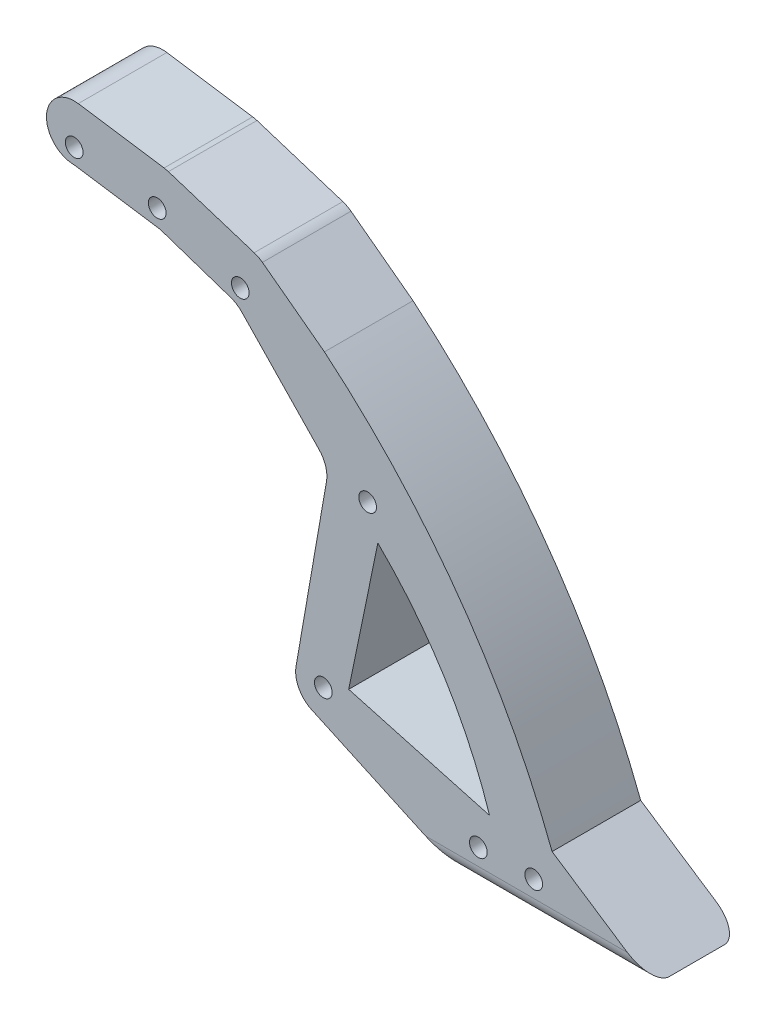
SolidWorks part; units mm, degrees
note: The reader was unsure of these and kept them because the rebuilt part matched: shared geometry of "Sketch2<4>".
ref_plane "Front Plane" through (0, 0, 0) normal (0, 0, 1) x (1, 0, 0)
ref_plane "Top Plane" through (0, 0, 0) normal (0, 1, 0) x (1, 0, 0)
ref_plane "Right Plane" through (0, 0, 0) normal (1, 0, 0) x (0, 0, -1)
sketch "Sketch1" plane through (0, 0, 0) normal (0, 0, 1) x (1, 0, 0)
  line L0 (41.32, -5) -> (59.46, -17)
  line L1 (25, -17) -> (59.46, -17)
  line L5 (-12.4827, 61.7642) -> (-27.9827, 66.7007)
  line L6 (-28.7619, 66.8817) -> (-44.2619, 69.1952)
  line L7 (25, -17) -> (-2.089, -4.5427)
  line L8 (-45, 59.25) -> (-29.5, 56.9365)
  line L9 (0.2, 52.6) -> (-11, 61) construction
  line L10 (-29.5, 56.9365) -> (-15.5935, 52.2607)
  line L11 (-15.5935, 52.2607) -> (1, 35)
  line L12 (-28.7619, 66.8817) -> (-27.9827, 66.7007)
  line L13 (9.8511, 27.5193) -> (4.5811, 2.0033)
  line L14 (4.5811, 2.0033) -> (30.0199, -5)
  line L15 (-4.9263, 0.855) -> (1, 35) construction
  line L17 (-11, 61) -> (0.2, 52.6)
  line L18 (-4.9263, 0.855) -> (1, 35)
  circle A0 centre (0, 0) radius 1.6
  circle A1 centre (-15, 55) radius 1.6
  circle A2 centre (-30, 60) radius 1.6
  circle A4 centre (-45, 62) radius 1.6
  circle A5 centre (28, -11) radius 1.6
  circle A6 centre (38, -11) radius 1.6
  circle A7 centre (0, 0) radius 5
  circle A12 centre (-29.5, 61.9365) radius 5 construction
  circle A13 centre (-14, 57) radius 5 construction
  arc A14 (-44.2619, 69.1952) -> (-45, 59.25) centre (-45, 64.25) ccw
  arc A15 (-12.4827, 61.7642) -> (-11, 61) centre (-14, 57) cw
  arc A16 (0.2, 52.6) -> (41.32, -5) centre (-89.4843, -54.9022) cw
  arc A17 (9.8511, 27.5193) -> (30.0199, -5) centre (-46.0773, -29.6821) cw
  circle A18 centre (8, 33) radius 1.6
  point P15 (42.23, -11)
  dimension "D1" = 3.2
  dimension "D3" = 3.2
  dimension "D11" = 3.2
  dimension "D12" = 140
  dimension "D13" = 28
  dimension "D16" = 3.2
  dimension "D17" = 3.2
  dimension "D18" = 3.2
  dimension "D24" = 11.2
  dimension "D25" = 10
  dimension "D26" = 1
  dimension "D27" = 2
  dimension "D20" = 10
  dimension "D4" = 10
  dimension "D5" = 10
  dimension "D37" = 10
  dimension "D38" = 3.2
  dimension "D2" = 55
  dimension "D6" = 62
  dimension "D7" = 45
  dimension "D8" = 30
  dimension "D9" = 60
  dimension "D10" = 15
  dimension "D14" = 38
  dimension "D15" = 11
  dimension "D19" = 11
  dimension "D21" = 3
  dimension "D22" = 21.46
  dimension "D23" = 3.32
  dimension "D28" = 6
  dimension "D29" = 6
  dimension "D30" = 8.4
  dimension "D31" = 0.5
  dimension "D32" = 2
  dimension "D33" = 0
  dimension "D34" = 2.25
  dimension "D35" = 35
  dimension "D36" = 1
  dimension "D39" = 33
  dimension "D40" = 8
extrude "Boss-Extrude1" add sketch "Sketch1" along normal blind 16
fillet "Fillet1" radius 3 2 edges at (42.23, -17, 0) (42.23, -17, 16)
fillet "Fillet2" radius 5 3 edges at (1, 35, 8) (-29.5, 56.9365, 8) (-15.5935, 52.2607, 8)
sketch "Sketch2" plane through (0, 0, 16) normal (0, 0, 1) x (1, 0, 0)
  line L0 (-17.9796, 59.0152) -> (-23.4996, 54.919)
  line L5 (-10, 55) -> (-10, 46.4423)
  line L6 (-29.0814, 56.7957) -> (-16.7552, 52.6513) construction
  line L7 (-23.4996, 54.919) -> (-10, 46.4423)
  line L8 (-33.6358, 63.4323) -> (-38.5, 58.2798)
  line L9 (-25.1633, 61.2675) -> (-23.4996, 54.919)
  line L10 (-38.5, 58.2798) -> (-23.4996, 54.919)
  line L11 (-45, 59.25) -> (-29.9368, 57.0017) construction
  line L12 (-13.2054, 53.9095) -> (-14.7441, 51.3772)
  line L13 (-16.7998, 56.0821) -> (-18.5081, 53.2407)
  line L14 (-32.0814, 60.2786) -> (-32.4695, 57.3797)
  line L15 (-27.9194, 59.7155) -> (-28.3521, 56.5505)
  line L17 (-40.2538, 63.5727) -> (-38.5, 58.2798)
  line L19 (-42.9322, 61.6338) -> (-43.3967, 59.0107)
  line L20 (-47.0684, 62.363) -> (-47.4974, 59.9184)
  line L21 (-14.7441, 51.3772) -> (-0.7548, 36.8254) construction
  circle A0 centre (-30, 60) radius 5
  circle A1 centre (-15, 55) radius 5
  circle A2 centre (-30, 60) radius 1.6 construction
  circle A3 centre (-15, 55) radius 2.1
  circle A4 centre (-30, 60) radius 2.1
  circle A5 centre (-45, 62) radius 5
  circle A6 centre (-45, 62) radius 2.1
  circle A7 centre (-45, 62) radius 1.6 construction
  arc A8 (-44.2619, 69.1952) -> (-45, 59.25) centre (-45, 64.25) ccw construction
  circle M25 centre (-45, 62) radius 1.6
  circle M26 centre (-30, 60) radius 1.6
  circle M27 centre (-15, 55) radius 1.6
  arc M32 (-44.2619, 69.1952) -> (-45, 59.25) centre (-45, 64.25) ccw
  line M33 (-45, 59.25) -> (-29.9368, 57.0017)
  arc M34 (-29.9368, 57.0017) -> (-29.0814, 56.7957) centre (-30.6749, 52.0565) cw
  line M35 (-29.0814, 56.7957) -> (-16.7552, 52.6513)
  arc M36 (-16.7552, 52.6513) -> (-14.7441, 51.3772) centre (-18.3486, 47.912) cw
  dimension "D3" = 8.5
  dimension "D1" = 10
  dimension "D4" = 10
  dimension "D6" = 4.2
  dimension "D8" = 4.2
  dimension "D9" = 4.2
  dimension "D10" = 10
  dimension "D12" = 4.2
  dimension "D2" = 5
  dimension "D5" = 8.5
  dimension "D7" = 4.2
  dimension "D11" = 4.2
extrude "Cut-Extrude1" cut sketch "Sketch2" against normal blind 5 from offset 5.5 offset against normal yes
extrude "Cut-Extrude2" cut sketch "Sketch2<4>" against normal blind 8 from offset 4 contours A4 L14 L15 M33 M34 M35 | A4 M26 | A6 M25 | A6 L20 L19 M32 M33 | A3 L12 M36 | A3 M27 offset against normal yes
sketch "Sketch2<4>" plane through (0, 0, 16) normal (0, 0, 1) x (1, 0, 0) same geometry as "Sketch2"
fillet "Fillet3" radius 1 12 edges at (-32.4695, 57.3797, 11.25) (-32.4695, 57.3797, 4.75) (-28.3521, 56.5505, 11.25) (-28.3521, 56.5505, 4.75) (-14.7441, 51.3772, 4.75) (-14.7441, 51.3772, 11.25) (-18.5081, 53.2407, 11.25) (-18.5081, 53.2407, 4.75) (-47.4974, 59.9184, 4.75) (-47.4974, 59.9184, 11.25) (-43.3967, 59.0107, 11.25) (-43.3967, 59.0107, 4.75)
